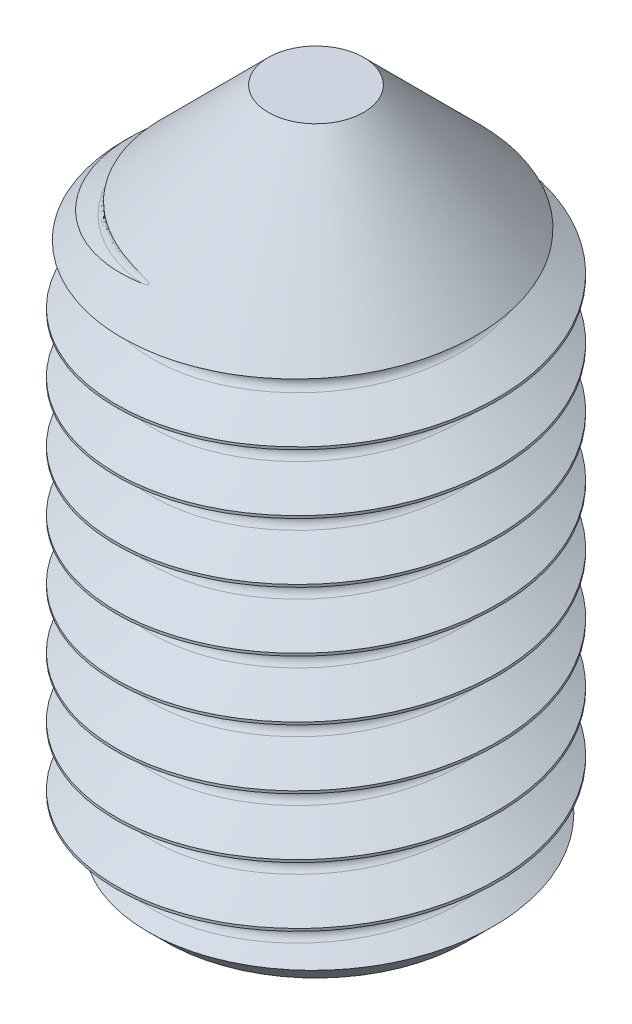
SolidWorks part; units mm, degrees
ref_plane "Front Plane" through (0, 0, 0) normal (0, 0, 1) x (1, 0, 0)
ref_plane "Top Plane" through (0, 0, 0) normal (0, 1, 0) x (1, 0, 0)
ref_plane "Right Plane" through (0, 0, 0) normal (1, 0, 0) x (0, 0, -1)
sketch "Sketch1" plane through (0, 0, 0) normal (0, 1, 0) x (1, 0, 0)
  circle A0 centre (0, 0) radius 4
  dimension "D1" = 8
extrude "Boss-Extrude1" add sketch "Sketch1" along normal mid plane 14
sketch "Sketch2" plane through (0, 0, 0) normal (0, 0, 1) x (1, 0, 0)
  line L0 (1, 7) -> (7.0082, 0.9918)
  line L1 (7.0082, 0.9918) -> (7.0082, -3.1418)
  line L2 (7.0082, -3.1418) -> (3.15, -7)
  line L3 (3.15, -7) -> (3.15, -11.4405)
  line L4 (3.15, -11.4405) -> (10.7214, -11.4405)
  line L5 (10.7214, -11.4405) -> (10.7214, 12.2044)
  line L6 (10.7214, 12.2044) -> (1, 12.2044)
  line L7 (1, 12.2044) -> (1, 7)
  line L8 (0, 0) -> (0, -3.1523) construction
  line L9 (4, 7) -> (-4, 7) construction
  line L10 (-4, -7) -> (4, -7) construction
  dimension "D1" = 2
  dimension "D2" = 6.3
  dimension "D3" = 135
  dimension "D4" = 135
revolve "Cut-Revolve1" cut sketch "Sketch2" angle 360 about L8
sketch "Sketch3" plane through (0, -7, 0) normal (0, -1, 0) x (1, 0, 0)
  line L1 (2.045, -1.1807) -> (2.045, 1.1807)
  line L2 (2.045, 1.1807) -> (0, 2.3614)
  line L3 (0, 2.3614) -> (-2.045, 1.1807)
  line L4 (-2.045, 1.1807) -> (-2.045, -1.1807)
  line L5 (-2.045, -1.1807) -> (0, -2.3614)
  line L6 (0, -2.3614) -> (2.045, -1.1807)
  circle A0 centre (0, 0) radius 2.045 construction
  dimension "D1" = 4.09
extrude "Cut-Extrude1" cut sketch "Sketch3" against normal blind 4
sketch "Sketch4" plane through (0, -7, 0) normal (0, -1, 0) x (1, 0, 0)
  circle A0 centre (0, 0) radius 4 construction
  circle A1 centre (0, 0) radius 4
curve "Helix/Spiral1" pitch 1.25 height 18.125 radius 4 centre (0, -7, 0) axis (0, 1, 0) start towards (0, 0, -1)
sketch "Sketch5" plane through (0, 0, 0) normal (0, 0, 1) x (1, 0, 0)
  line L1 (4.0456, -6.612) -> (3.2337, -7.0807)
  line L2 (3.2337, -7.3932) -> (4.0456, -7.8619)
  line L3 (4.0456, -7.8619) -> (4.0456, -6.612)
  circle A0 centre (3.6848, -7.237) radius 0.3608 construction
  arc A1 (3.2337, -7.0807) -> (3.2337, -7.3932) centre (3.3239, -7.237) ccw
  point P7 (3.778, -7.0194)
  point P8 (3.6848, -7.237)
  dimension "D2" = 0.1804
  dimension "D1" = 1.2499
sweep "Cut-Sweep1" cut profiles "Sketch5" path "Helix/Spiral1" align with end faces yes
sketch "Sketch6" plane through (0, -7, 0) normal (0, -1, 0) x (1, 0, 0)
  circle A0 centre (0, 0) radius 2.3614
extrude "Cut-Extrude2" cut sketch "Sketch6" against normal blind 1.5 draft 75
